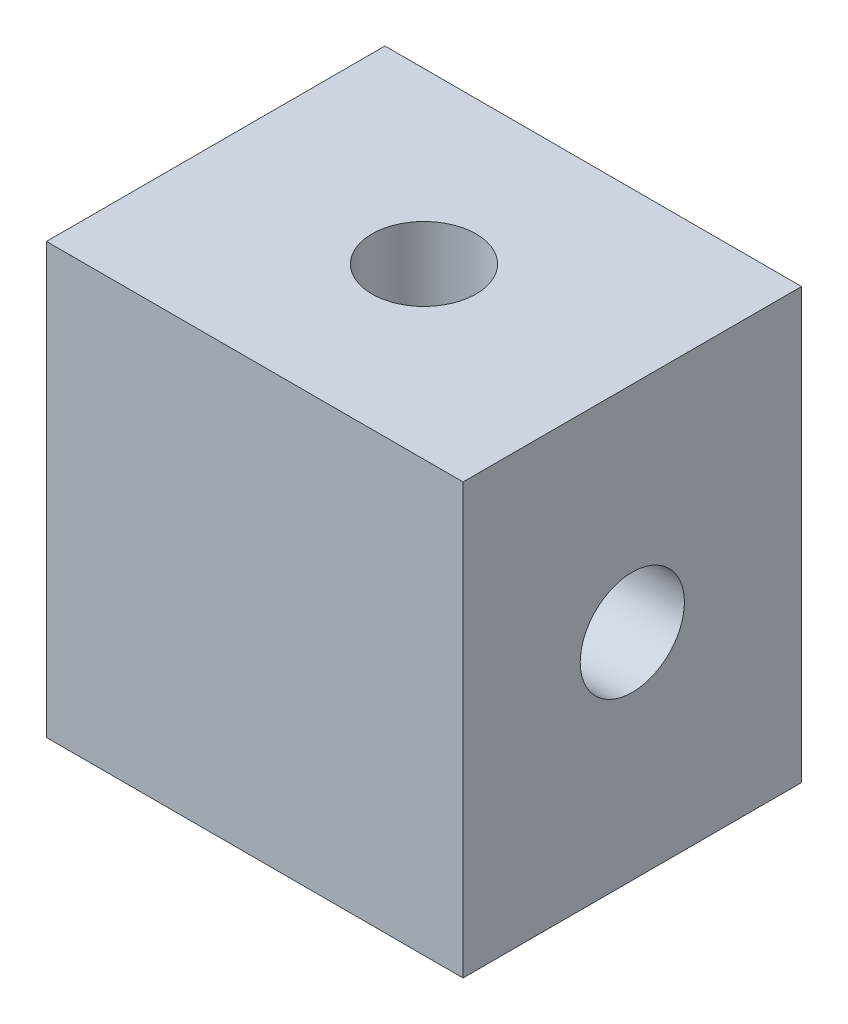
SolidWorks part; units mm, degrees
material "AISI 1045 Steel, cold drawn"
ref_plane "Front Plane" through (0, 0, 0) normal (0, 0, 1) x (1, 0, 0)
ref_plane "Top Plane" through (0, 0, 0) normal (0, 1, 0) x (1, 0, 0)
ref_plane "Right Plane" through (0, 0, 0) normal (1, 0, 0) x (0, 0, -1)
ref_plane "PL_Block_base" through (0, 0, -13) normal (0, 0, 1) x (1, 0, 0)
sketch "SK_Block" plane through (0, 0, -13) normal (0, 0, 1) x (1, 0, 0)
  line L0 (-16, -16.5) -> (16, -16.5)
  line L1 (16, -16.5) -> (16, 16.5)
  line L2 (16, 16.5) -> (-16, 16.5)
  line L3 (-16, 16.5) -> (-16, -16.5)
  dimension "P1" = 16
  dimension "P2" = 16.5
  dimension "P3" = 16
  dimension "P4" = 16.5
  dimension "P5" = 16
  dimension "P6" = 16.5
  dimension "P7" = 16
  dimension "P8" = 16.5
extrude "Block" add sketch "SK_Block" along normal blind 26
ref_plane "PL_Pitch_Bore_base" through (0, -20, 0) normal (0, 1, 0) x (1, 0, 0)
sketch "SK_Pitch_Bore" plane through (0, -20, 0) normal (0, 1, 0) x (1, 0, 0)
  circle A0 centre (0, 0) radius 4
  dimension "D1_SK_Pitch_Bore" = 8
extrude "Pitch_Bore" cut sketch "SK_Pitch_Bore" along normal blind 40
ref_plane "PL_Roll_Bore_base" through (-20, 0, 0) normal (1, 0, 0) x (0, 0, -1)
sketch "SK_Roll_Bore" plane through (-20, 0, 0) normal (1, 0, 0) x (0, 0, -1)
  circle A0 centre (0, 0) radius 4
  dimension "D1_SK_Roll_Bore" = 8
extrude "Roll_Bore" cut sketch "SK_Roll_Bore" along normal blind 40
ref_axis "AX_Pitch" through (0, 18.15, 0) along (0, -1, 0)
ref_axis "AX_Roll" through (-17.6, 0, 0) along (1, 0, 0)
equation "\"Cross_size\"= 32"
